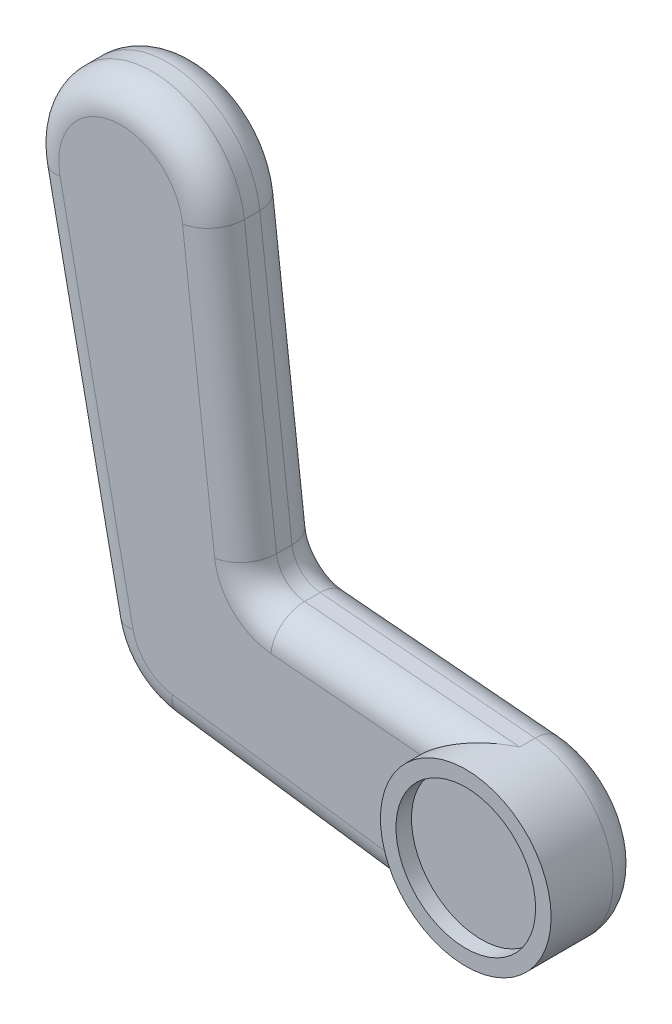
SolidWorks part; units mm, degrees
ref_plane "前视基准面" through (0, 0, 0) normal (0, 0, 1) x (1, 0, 0)
ref_plane "上视基准面" through (0, 0, 0) normal (0, 1, 0) x (1, 0, 0)
ref_plane "右视基准面" through (0, 0, 0) normal (1, 0, 0) x (0, 0, -1)
other "Configuration Table"
sketch "草图1" plane through (0, 0, 0) normal (0, 0, 1) x (1, 0, 0)
  circle A0 centre (0, 0) radius 22.5
  circle A1 centre (0, 0) radius 27.5
  dimension "D1" = 45
  dimension "D2" = 55
extrude "凸台-拉伸1" add sketch "草图1" along normal blind 5
sketch "草图2" plane through (0, 0, 0) normal (0, 0, -1) x (-1, 0, 0)
  line L0 (3.7575, -27.2421) -> (100.932, -13.8387)
  line L1 (-2.365, 27.3981) -> (75.0661, 34.0819)
  line L2 (145.5582, 120.7459) -> (122.0063, 5.9043)
  line L3 (86.3751, 130.2757) -> (75.0661, 34.0819)
  circle A0 centre (0, 0) radius 27.5
  arc A1 (100.932, -13.8387) -> (122.0063, 5.9043) centre (97.516, 10.9268) ccw
  arc A2 (145.5582, 120.7459) -> (86.3751, 130.2757) centre (116.1699, 126.7729) ccw
  circle M8 centre (0, 0) radius 27.5
  circle M9 centre (0, 0) radius 22.5
  dimension "D1" = 60
  dimension "D2" = 50
  dimension "D3" = 55
extrude "凸台-拉伸2" add sketch "草图2" along normal blind 25 contours L2 A2 L3 L1 L0 A1 M8 | M9 | M8 M9 region at (-93.1212, 56.7883, 0) region at (26.556, -2.9756, 0) region at (0, 0, 0)
fillet "圆角1" radius 10 8 edges at (-36.3505, 30.74, -25) (27.329, -3.0623, -25) (-52.3447, -20.5404, -25) (-114.608, -7.3177, -25) (-120.9391, 156.3914, -25) (-133.7823, 63.3251, -25) (-80.7206, 82.1788, -25) (-75.0661, 34.0819, -12.5)
fillet "圆角2" radius 10 7 edges at (-52.3447, -20.5404, 0) (-114.608, -7.3177, 0) (-120.9391, 156.3914, 0) (-32.2906, 30.3896, 0) (-73.047, 36.1644, 0) (-133.7823, 63.3251, 0) (-81.1964, 86.226, 0)
